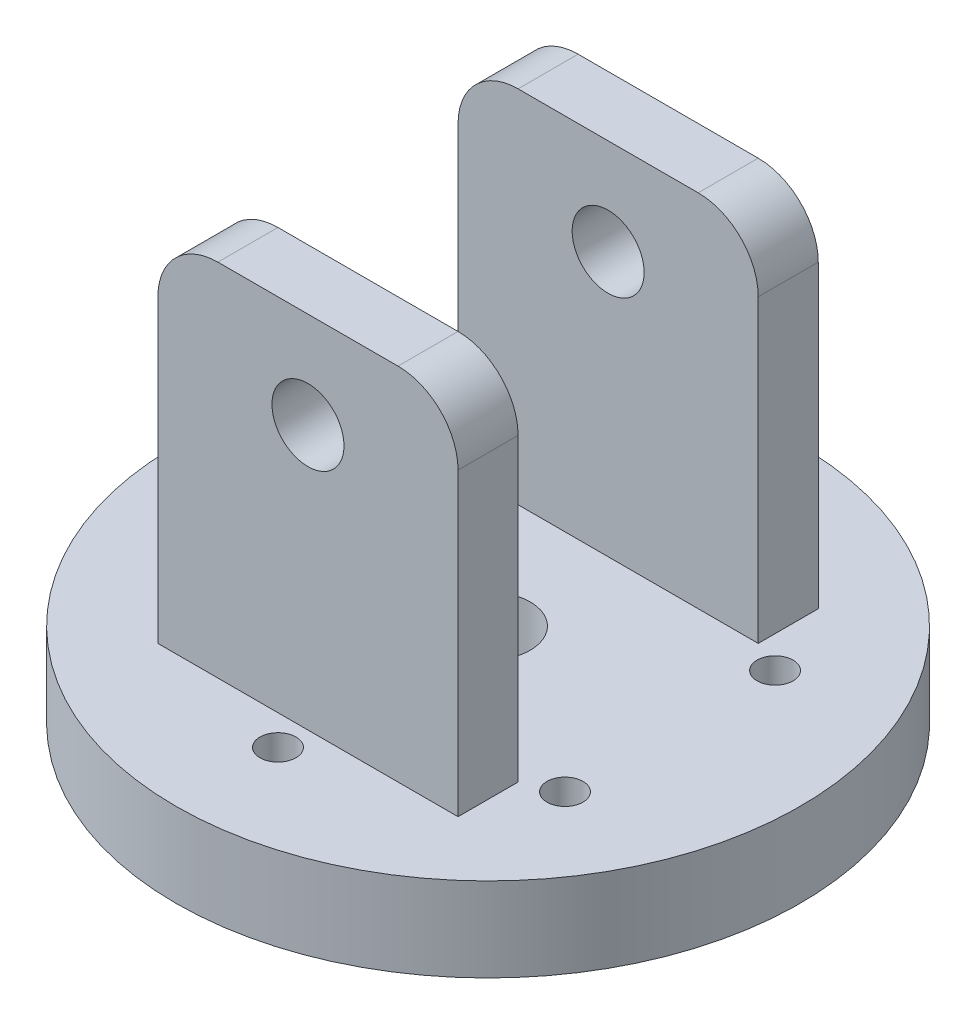
SolidWorks part; units mm, degrees
ref_plane "Plan de face" through (0, 0, 0) normal (0, 0, 1) x (1, 0, 0)
ref_plane "Plan de dessus" through (0, 0, 0) normal (0, 1, 0) x (1, 0, 0)
ref_plane "Plan de droite" through (0, 0, 0) normal (1, 0, 0) x (0, 0, -1)
sketch "Esquisse1" plane through (0, 0, 0) normal (0, 1, 0) x (1, 0, 0)
  circle A0 centre (0, 0) radius 52
  circle A1 centre (0, 0) radius 7
  dimension "D1" = 104
  dimension "D2" = 14
extrude "Boss.-Extru.1" add sketch "Esquisse1" along normal blind 14
sketch "Esquisse2" plane through (0, 14, 0) normal (0, 1, 0) x (1, 0, 0)
  line L0 (0, 0) -> (0, 25) construction
  line L1 (25, 20) -> (-25, 20)
  line L2 (25, 20) -> (25, 30)
  line L3 (-25, 20) -> (-25, 30)
  line L4 (25, 30) -> (-25, 30)
  line L5 (25, 20) -> (-25, 30) construction
  line L6 (-25, 20) -> (25, 30) construction
  line L7 (-34.3845, 0) -> (33.9668, 0) construction
  dimension "D1" = 25
  dimension "D2" = 50
  dimension "D3" = 10
extrude "Boss.-Extru.2" add sketch "Esquisse2" along normal blind 60
fillet "Congé1" radius 10 2 edges at (25, 74, -25) (-25, 74, -25)
sketch "Esquisse3" plane through (0, 0, -30) normal (0, 0, -1) x (-1, 0, 0)
  line L0 (-15, 74) -> (15, 74) construction
  line L1 (25, 64) -> (25, 14) construction
  circle A0 centre (0, 58) radius 6
  dimension "D1" = 16
  dimension "D2" = 12
  dimension "D3" = 25
extrude "Enlèv. mat.-Extru.1" cut sketch "Esquisse3" against normal blind 40
pattern_circular "Répétition circulaire1" count 2 over 360 about axis through (0, 14, 0) along (0, 1, 0) of "Boss.-Extru.2", "Congé1", "Enlèv. mat.-Extru.1"
sketch "Esquisse5" plane through (0, 0, 0) normal (0, -1, 0) x (1, 0, 0)
  circle A0 centre (0, 0) radius 35 construction
  circle A1 centre (0, 35) radius 2.5
  dimension "D1" = 70
  dimension "D2" = 5
extrude "Enlèv. mat.-Extru.2" cut sketch "Esquisse5" against normal blind 20
pattern_circular "Répétition circulaire2" count 6 over 360 about axis through (0, 0, 0) along (0, 1, 0) of "Enlèv. mat.-Extru.2"
sketch "Esquisse6" plane through (0, 14, 0) normal (0, 1, 0) x (1, 0, 0)
  circle A0 centre (30.3109, 17.5) radius 3
  circle A1 centre (30.3109, -17.5) radius 3
  circle A2 centre (0, -35) radius 3
  circle A3 centre (-30.3109, -17.5) radius 3
  circle A4 centre (-30.3109, 17.5) radius 3
  circle A5 centre (0, 35) radius 3
  point P16 (0, 0)
  dimension "D1" = 6
  dimension "D2" = 6
extrude "Enlèv. mat.-Extru.3" cut sketch "Esquisse6" against normal blind 11
